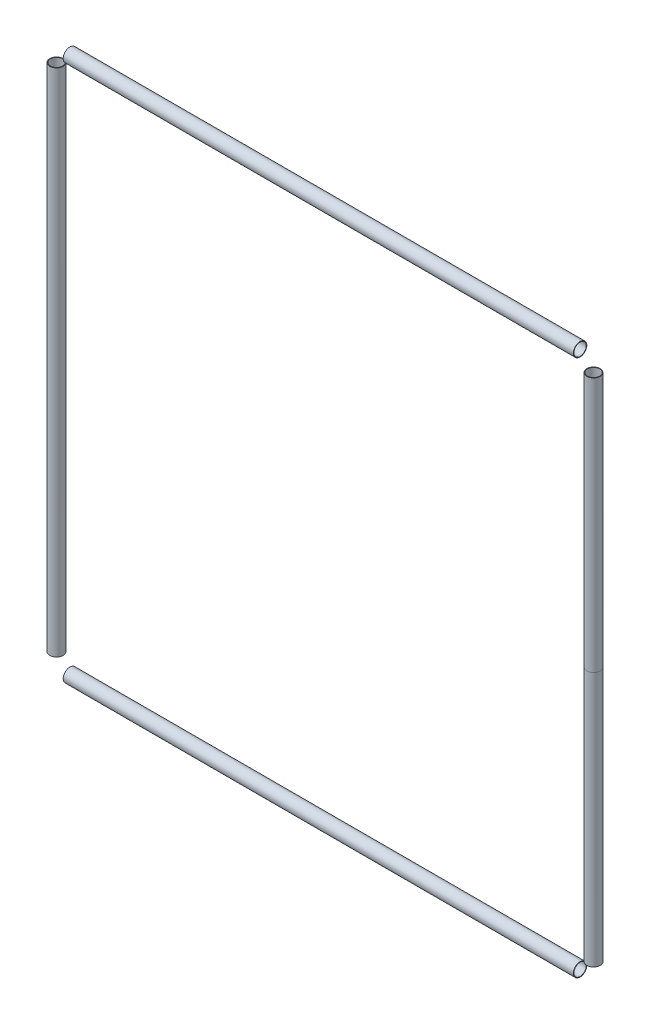
SolidWorks part; units mm, degrees
material "6061-T6 (SS)"
ref_plane "Front Plane" through (0, 0, 0) normal (0, 0, 1) x (1, 0, 0)
ref_plane "Top Plane" through (0, 0, 0) normal (0, 1, 0) x (1, 0, 0)
ref_plane "Right Plane" through (0, 0, 0) normal (1, 0, 0) x (0, 0, -1)
sketch "Sketch1" plane through (0, 0, 0) normal (0, 0, 1) x (1, 0, 0)
  line L1 (-127, 127) -> (127, 127)
  line L2 (-127, 127) -> (-127, -127)
  line L3 (-127, -127) -> (127, -127)
  line L4 (127, 127) -> (127, -127)
  line L5 (-127, 127) -> (127, -127) construction
  line L6 (-127, -127) -> (127, 127) construction
  point P0 (0, 0)
  dimension "D1" = 254
sketch "Sketch3" plane through (0, 0, 0) normal (0, 1, 0) x (1, 0, 0)
  circle A0 centre (127, 0) radius 3.175
  circle A1 centre (127, 0) radius 2.921
  dimension "D1" = 6.35
  dimension "D2" = 0.254
sweep "Sweep1" add profiles "Sketch3" path "Sketch1"
sketch "Sketch4" plane through (0, 0, 0) normal (0, 0, 1) x (1, 0, 0)
  line L0 (-127, -127) -> (127, 127) construction
  line L1 (133.35, 133.35) -> (120.65, 133.35)
  line L2 (133.35, 133.35) -> (133.35, 120.65)
  line L3 (133.35, 120.65) -> (120.65, 120.65)
  line L4 (120.65, 133.35) -> (120.65, 120.65)
  line L5 (127, 120.65) -> (127, 133.35) construction
  line L6 (133.35, 127) -> (120.65, 127) construction
  line L7 (-127, 127) -> (127, -127) construction
  line L8 (-133.35, 133.35) -> (-120.65, 133.35)
  line L9 (-133.35, 133.35) -> (-133.35, 120.65)
  line L10 (-133.35, 120.65) -> (-120.65, 120.65)
  line L11 (-120.65, 133.35) -> (-120.65, 120.65)
  line L12 (-127, 120.65) -> (-127, 133.35) construction
  line L13 (-133.35, 127) -> (-120.65, 127) construction
  line L15 (-133.35, -133.35) -> (-120.65, -133.35)
  line L16 (-133.35, -133.35) -> (-133.35, -120.65)
  line L17 (-133.35, -120.65) -> (-120.65, -120.65)
  line L18 (-120.65, -133.35) -> (-120.65, -120.65)
  line L19 (-127, -120.65) -> (-127, -133.35) construction
  line L20 (-133.35, -127) -> (-120.65, -127) construction
  line L21 (133.35, -133.35) -> (120.65, -133.35)
  line L22 (133.35, -133.35) -> (133.35, -120.65)
  line L23 (133.35, -120.65) -> (120.65, -120.65)
  line L24 (120.65, -133.35) -> (120.65, -120.65)
  line L25 (127, -120.65) -> (127, -133.35) construction
  line L26 (133.35, -127) -> (120.65, -127) construction
  point P0 (127, 127)
  point P6 (-127, 127)
  point P12 (-127, -127)
  point P16 (127, -127)
  dimension "D1" = 12.7
extrude "Cut-Extrude1" cut sketch "Sketch4" against normal through all both and the other way through all
